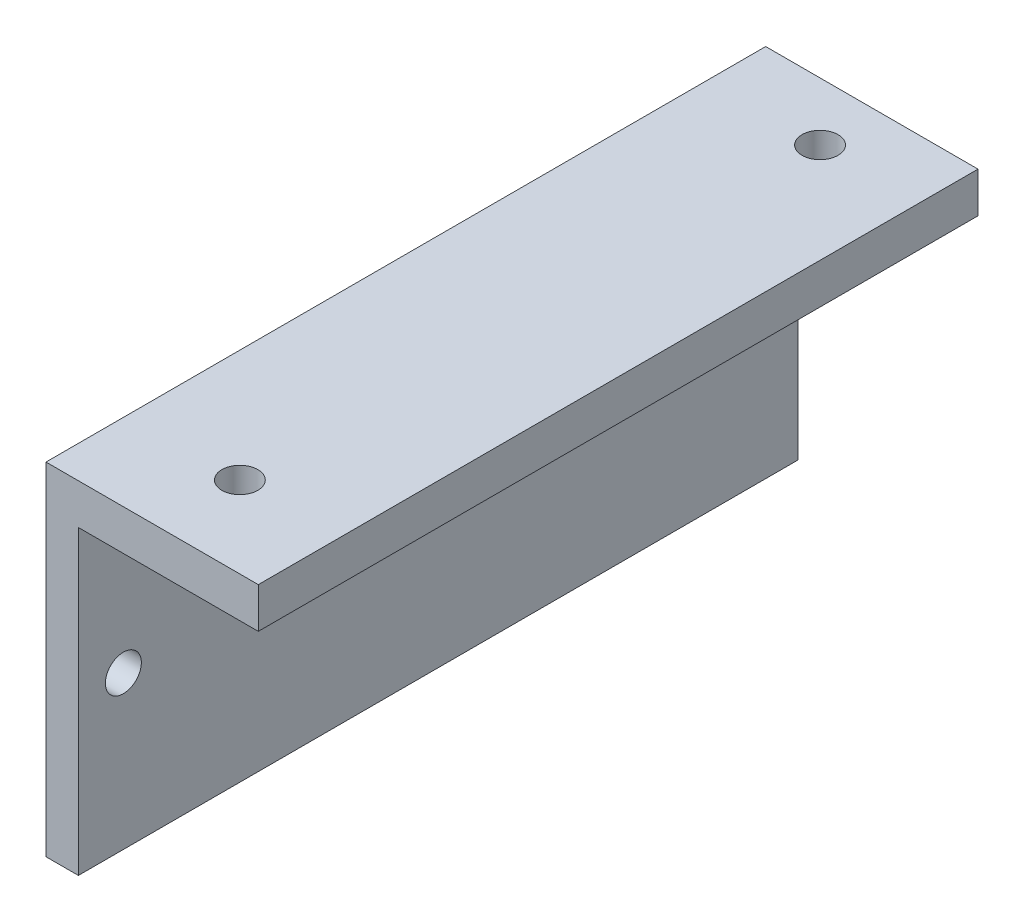
SolidWorks part; units mm, degrees
ref_plane "Front Plane" through (0, 0, 0) normal (0, 0, 1) x (1, 0, 0)
ref_plane "Top Plane" through (0, 0, 0) normal (0, 1, 0) x (1, 0, 0)
ref_plane "Right Plane" through (0, 0, 0) normal (1, 0, 0) x (0, 0, -1)
sketch "Sketch1" plane through (0, 0, 0) normal (1, 0, 0) x (0, 0, -1)
  line L0 (-35, -2) -> (35, -2) construction
  line L1 (-40, 19) -> (40, 19)
  line L2 (-40, 19) -> (-40, -19)
  line L3 (-40, -19) -> (40, -19)
  line L4 (40, 19) -> (40, -19)
  line L5 (0, -19) -> (0, 19) construction
  line L6 (-40, 0) -> (40, 0) construction
  line L7 (-40, 14.5) -> (40, 14.5)
  circle A0 centre (-35, -2) radius 2
  circle A1 centre (35, -2) radius 2
  point P0 (0, 0)
  point P7 (0, -2)
  dimension "D6" = 4
  dimension "D7" = 4
  dimension "D1" = 80
  dimension "D2" = 33.5
  dimension "D3" = 70
  dimension "D4" = 4.5
  dimension "D5" = 16.5
extrude "Boss-Extrude1" add sketch "Sketch1" along normal blind 23.6 contours L2 L7 L4 L1 region at (0, 16.75, 0)
extrude "Boss-Extrude2" add sketch "Sketch1<4>" along normal blind 3.6 contours L7 L2 L3 L4 A1 A0 region at (0, -2.2524, 0)
sketch "Sketch1<4>" plane through (0, 0, 0) normal (1, 0, 0) x (0, 0, -1) same geometry as "Sketch1"
sketch "Sketch2" plane through (0, 19, 0) normal (0, 1, 0) x (1, 0, 0)
  line L0 (12.5, -30.9509) -> (12.5, 34.0491)
  line L1 (0, -40) -> (0, 40) construction
  circle A0 centre (12.5, -30.9509) radius 2
  circle A1 centre (12.5, 33.5413) radius 2
  point P3 (12.5, 1.5491)
  dimension "D3" = 4
  dimension "D4" = 4
  dimension "D1" = 65
  dimension "D2" = 12.5
extrude "Cut-Extrude1" cut sketch "Sketch2" against normal up to next contours A0 | A1 region at (11.1258, 19, -34.9155) region at (13.8742, 19, 29.5767)
